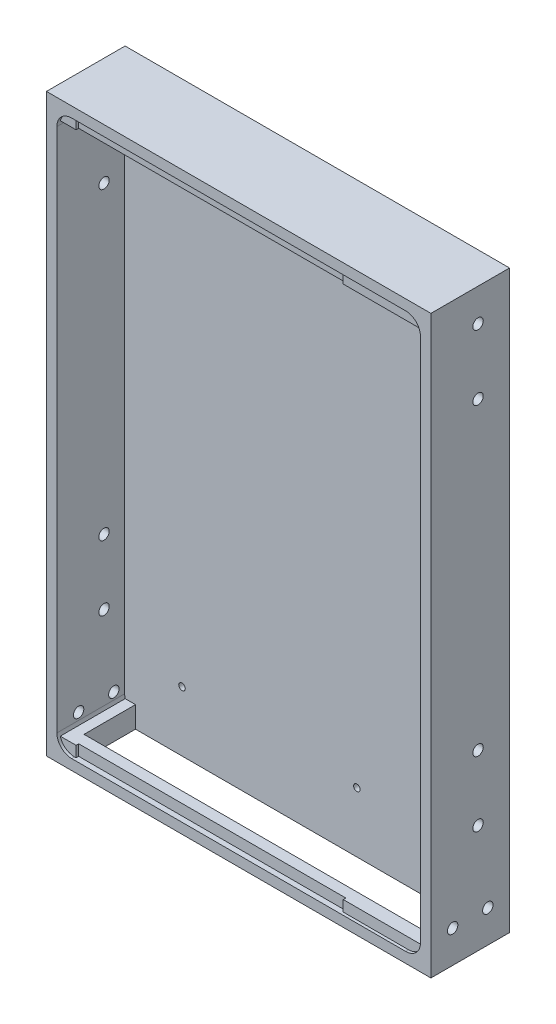
SolidWorks part; units mm, degrees
ref_plane "Front Plane" through (0, 0, 0) normal (0, 0, 1) x (1, 0, 0)
ref_plane "Top Plane" through (0, 0, 0) normal (0, 1, 0) x (1, 0, 0)
ref_plane "Right Plane" through (0, 0, 0) normal (1, 0, 0) x (0, 0, -1)
sketch "Sketch1" plane through (0, 0, 0) normal (0, 0, 1) x (1, 0, 0)
  line L1 (-88.5, -132.5) -> (88.5, -132.5)
  line L2 (-88.5, -132.5) -> (-88.5, 132.5)
  line L3 (-88.5, 132.5) -> (88.5, 132.5)
  line L4 (88.5, -132.5) -> (88.5, 132.5)
  line L5 (-88.5, -132.5) -> (88.5, 132.5) construction
  line L6 (-88.5, 132.5) -> (88.5, -132.5) construction
  circle A0 centre (-57.3, -104.9) radius 1.5 construction
  circle A1 centre (23.21, -104.9) radius 1.5 construction
  circle A2 centre (23.21, 104.9) radius 1.5 construction
  circle A3 centre (-57.3, 104.9) radius 1.5 construction
  circle A4 centre (-57.3, -104.9) radius 1.5
  circle A5 centre (23.21, -104.9) radius 1.5
  circle A6 centre (23.21, 104.9) radius 1.5
  circle A7 centre (-57.3, 104.9) radius 1.5
  point P0 (0, 0)
  dimension "D1" = 177
  dimension "D2" = 265
extrude "Boss-Extrude1" add sketch "Sketch1" along normal blind 5
sketch "Sketch2" plane through (0, 0, 5) normal (0, 0, 1) x (1, 0, 0)
  line L0 (83.7, -127.7) -> (83.7, 127.7)
  line L1 (83.7, 127.7) -> (-83.7, 127.7)
  line L2 (-83.7, 127.7) -> (-83.7, -127.7)
  line L3 (-83.7, -127.7) -> (83.7, -127.7)
  line L4 (88.5, -132.5) -> (88.5, 132.5)
  line L5 (88.5, 132.5) -> (-88.5, 132.5)
  line L6 (-88.5, 132.5) -> (-88.5, -132.5)
  line L7 (-88.5, -132.5) -> (88.5, -132.5)
  line L8 (88.5, -132.5) -> (88.5, 132.5)
  line L9 (88.5, 132.5) -> (-88.5, 132.5)
  line L10 (-88.5, 132.5) -> (-88.5, -132.5)
  line L11 (-88.5, -132.5) -> (88.5, -132.5)
  dimension "D1" = 0
  dimension "D2" = 4.8
extrude "Boss-Extrude2" add sketch "Sketch2" along normal blind 31.2
fillet "Fillet1" radius 6.82 4 edges at (83.7, 127.7, 20.6) (83.7, -127.7, 20.6) (-83.7, -127.7, 20.6) (-83.7, 127.7, 20.6)
sketch "Sketch4" plane through (0, 0, 5) normal (0, 0, 1) x (1, 0, 0)
  line L0 (-83.7, 122.7) -> (83.7, 122.7)
  line L1 (-83.7, -122.7) -> (83.7, -122.7)
  line L4 (83.7, -120.88) -> (83.7, 120.88)
  line L5 (76.88, 127.7) -> (-76.88, 127.7)
  line L6 (-83.7, 120.88) -> (-83.7, -120.88)
  line L7 (-76.88, -127.7) -> (76.88, -127.7)
  line L8 (83.7, -120.88) -> (83.7, 120.88)
  line L9 (76.88, 127.7) -> (-76.88, 127.7)
  line L10 (-83.7, 120.88) -> (-83.7, -120.88)
  line L11 (-76.88, -127.7) -> (76.88, -127.7)
  arc A4 (83.7, 120.88) -> (76.88, 127.7) centre (76.88, 120.88) ccw
  arc A5 (-76.88, 127.7) -> (-83.7, 120.88) centre (-76.88, 120.88) ccw
  arc A6 (-83.7, -120.88) -> (-76.88, -127.7) centre (-76.88, -120.88) ccw
  arc A7 (76.88, -127.7) -> (83.7, -120.88) centre (76.88, -120.88) ccw
  arc A8 (83.7, 120.88) -> (76.88, 127.7) centre (76.88, 120.88) ccw
  arc A9 (-76.88, 127.7) -> (-83.7, 120.88) centre (-76.88, 120.88) ccw
  arc A10 (-83.7, -120.88) -> (-76.88, -127.7) centre (-76.88, -120.88) ccw
  arc A11 (76.88, -127.7) -> (83.7, -120.88) centre (76.88, -120.88) ccw
  arc M12 (83.7, 120.88) -> (76.88, 127.7) centre (76.88, 120.88) ccw
  line M13 (76.88, 127.7) -> (-76.88, 127.7)
  arc M14 (-76.88, 127.7) -> (-83.7, 120.88) centre (-76.88, 120.88) ccw
  arc M16 (-83.7, -120.88) -> (-76.88, -127.7) centre (-76.88, -120.88) ccw
  line M17 (-76.88, -127.7) -> (76.88, -127.7)
  arc M18 (76.88, -127.7) -> (83.7, -120.88) centre (76.88, -120.88) ccw
  dimension "D2" = 5
  dimension "D3" = 5
  dimension "D1" = 0
extrude "Boss-Extrude3" add sketch "Sketch4" along normal offset from surface (29.9 mm away) 1.3 contours L1 M16 M17 M18 | L0 M14 M12 M13 region at (0, 125.1751, 5) region at (0, -125.1751, 5) up to face at (0, 0, 36.2)
sketch "Sketch5" plane through (0, 0, 34.9) normal (0, 0, 1) x (1, 0, 0)
  line L0 (83.4527, -122.7) -> (-83.4527, -122.7) construction
  line L1 (-76.88, -127.7) -> (76.88, -127.7) construction
  line L2 (76.88, 127.7) -> (-76.88, 127.7) construction
  line L3 (-83.4527, 122.7) -> (83.4527, 122.7) construction
  line L4 (83.4527, -122.7) -> (-83.4527, -122.7)
  line L5 (-76.88, -127.7) -> (76.88, -127.7)
  line L6 (76.88, 127.7) -> (-76.88, 127.7)
  line L7 (-83.4527, 122.7) -> (83.4527, 122.7)
  line L9 (-76.16, 127.7) -> (46.84, 127.7)
  line L10 (-76.16, 127.7) -> (-76.16, -127.7)
  line L11 (-76.16, -127.7) -> (46.84, -127.7)
  line L12 (46.84, 127.7) -> (46.84, -127.7)
  line L13 (-83.7, 120.88) -> (-83.7, -120.88) construction
  arc A0 (-83.4527, -122.7) -> (-76.88, -127.7) centre (-76.88, -120.88) ccw construction
  arc A1 (76.88, -127.7) -> (83.4527, -122.7) centre (76.88, -120.88) ccw construction
  arc A2 (-76.88, 127.7) -> (-83.4527, 122.7) centre (-76.88, 120.88) ccw construction
  arc A3 (83.4527, 122.7) -> (76.88, 127.7) centre (76.88, 120.88) ccw construction
  arc A4 (-83.4527, -122.7) -> (-76.88, -127.7) centre (-76.88, -120.88) ccw
  arc A5 (76.88, -127.7) -> (83.4527, -122.7) centre (76.88, -120.88) ccw
  arc A6 (-76.88, 127.7) -> (-83.4527, 122.7) centre (-76.88, 120.88) ccw
  arc A7 (83.4527, 122.7) -> (76.88, 127.7) centre (76.88, 120.88) ccw
  dimension "D1" = 7.54
  dimension "D2" = 123
extrude "Cut-Extrude1" cut sketch "Sketch5" against normal blind 1.2 contours L12 L4 L10 L5 | L12 L6 L10 L7 region at (-14.66, -125.2, 34.9) region at (-14.66, 125.2, 34.9)
sketch "Sketch9" plane through (0, -122.7, 0) normal (0, 1, 0) x (1, 0, 0)
  line L0 (-83.4527, -5) -> (83.4527, -5) construction
  line L1 (-78.7, -5) -> (78.7, -5)
  line L2 (-78.7, -5) -> (-78.7, -28.7)
  line L3 (-78.7, -28.7) -> (78.7, -28.7)
  line L4 (78.7, -5) -> (78.7, -28.7)
  line L5 (-83.7, -36.2) -> (-83.7, -5) construction
  line L6 (46.84, -33.7) -> (-76.16, -33.7) construction
  line L7 (83.7, -5) -> (83.7, -36.2) construction
  dimension "D1" = 5
  dimension "D2" = 5
  dimension "D3" = 5
extrude "Cut-Extrude3" cut sketch "Sketch9" against normal through all
sketch "Sketch10" plane through (88.5, 0, 0) normal (1, 0, 0) x (0, 0, -1)
  circle A0 centre (-10, -117.6) radius 2.4 construction
  circle A1 centre (-26.2, -117.6) radius 2.4 construction
  circle A2 centre (-10, -117.6) radius 2.4
  circle A3 centre (-26.2, -117.6) radius 2.4
extrude "Cut-Extrude4" cut sketch "Sketch10" against normal through all
sketch "Sketch11" plane through (0, 0, 0) normal (0, 0, -1) x (-1, 0, 0)
  line L0 (88.5, 132.5) -> (108.5, 132.5)
  line L1 (108.5, 132.5) -> (108.5, 82.5)
  line L2 (108.5, 82.5) -> (88.5, 82.5)
  line L3 (88.5, 132.5) -> (88.5, -132.5) construction
  line L4 (88.5, 82.5) -> (88.5, 132.5)
  line L9 (0, 132.5) -> (0, 0) construction
  line L10 (-88.5, 132.5) -> (88.5, 132.5) construction
  dimension "D1" = 50
  dimension "D2" = 20
sketch "Sketch16" plane through (88.5, 0, 0) normal (1, 0, 0) x (0, 0, -1)
  line L0 (0, -132.5) -> (0, 132.5) construction
  line L1 (-36.2, 132.5) -> (0, 132.5) construction
  line L2 (-14.5, 117.5) -> (-14.5, 87.5) construction
  line L3 (-14.5, 87.5) -> (-14.5, -52.5) construction
  line L4 (-14.5, -52.5) -> (-14.5, -82.5) construction
  line L8 (-36.2, 120.88) -> (-36.2, -120.88)
  line L9 (-36.2, -120.88) -> (-5, -120.88)
  line L10 (-5, -120.88) -> (-5, 120.88)
  line L11 (-5, 120.88) -> (-36.2, 120.88)
  line L16 (-36.2, 120.88) -> (-36.2, -120.88) construction
  line L17 (-36.2, -120.88) -> (-5, -120.88) construction
  line L18 (-5, -120.88) -> (-5, 120.88) construction
  line L19 (-5, 120.88) -> (-36.2, 120.88) construction
  circle A1 centre (-14.5, 117.5) radius 2.4
  circle A2 centre (-14.5, 87.5) radius 2.4
  circle A3 centre (-14.5, -52.5) radius 2.4
  circle A4 centre (-14.5, -82.5) radius 2.4
  dimension "D3" = 4.8
  dimension "D2" = 14.5
  dimension "D4" = 15
  dimension "D5" = 30
  dimension "D6" = 140
  dimension "D1" = 0
extrude "Cut-Extrude7" cut sketch "Sketch16" against normal up to surface (177 mm away) up to face at (-88.5, -117.6, 7.6)
